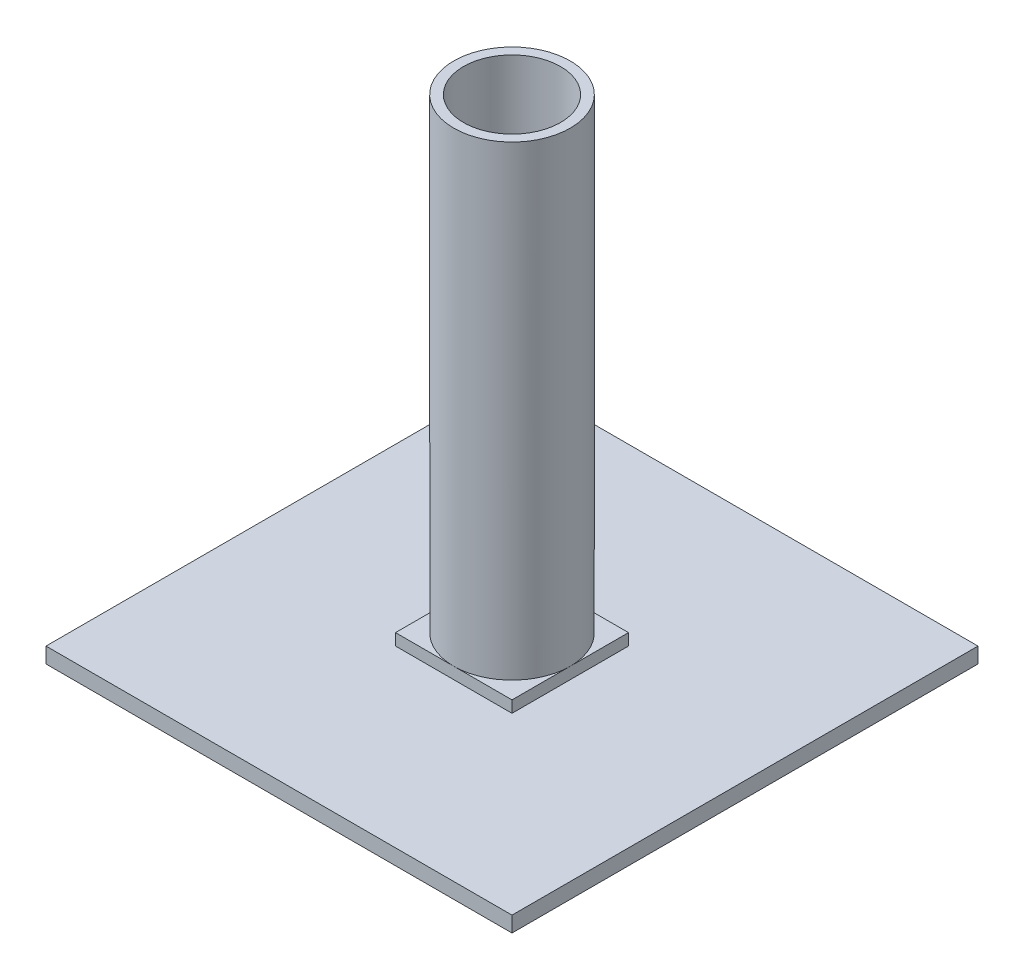
SolidWorks part; units mm, degrees
ref_plane "Front Plane" through (0, 0, 0) normal (0, 0, 1) x (1, 0, 0)
ref_plane "Top Plane" through (0, 0, 0) normal (0, 1, 0) x (1, 0, 0)
ref_plane "Right Plane" through (0, 0, 0) normal (1, 0, 0) x (0, 0, -1)
sketch "Sketch1" plane through (0, 0, 0) normal (0, 1, 0) x (1, 0, 0)
  circle A0 centre (0, 0) radius 38.1
  circle A1 centre (0, 0) radius 31.75
  dimension "D1" = 76.2
  dimension "D2" = 63.5
extrude "Boss-Extrude1" add sketch "Sketch1" along normal blind 304.8
sketch "Sketch2" plane through (0, 0, 0) normal (0, 1, 0) x (1, 0, 0)
  line L1 (-38.1, 38.1) -> (38.1, 38.1)
  line L2 (-38.1, 38.1) -> (-38.1, -38.1)
  line L3 (-38.1, -38.1) -> (38.1, -38.1)
  line L4 (38.1, 38.1) -> (38.1, -38.1)
  line L5 (-38.1, 38.1) -> (38.1, -38.1) construction
  line L6 (-38.1, -38.1) -> (38.1, 38.1) construction
  point P0 (0, 0)
  dimension "D1" = 76.2
  dimension "D2" = 76.2
extrude "Boss-Extrude2" add sketch "Sketch2" against normal blind 7.62
ref_plane "Plane1" through (0, -7.62, 0) normal (0, 1, 0) x (1, 0, 0)
sketch "Sketch4" plane through (0, -7.62, 0) normal (0, 1, 0) x (1, 0, 0)
  line L1 (152.4, -152.4) -> (-152.4, -152.4)
  line L2 (152.4, -152.4) -> (152.4, 152.4)
  line L3 (152.4, 152.4) -> (-152.4, 152.4)
  line L4 (-152.4, -152.4) -> (-152.4, 152.4)
  line L5 (152.4, -152.4) -> (-152.4, 152.4) construction
  line L6 (152.4, 152.4) -> (-152.4, -152.4) construction
  point P0 (0, 0)
  dimension "D1" = 304.8
  dimension "D2" = 304.8
extrude "Boss-Extrude4" add sketch "Sketch4" against normal blind 10.16
